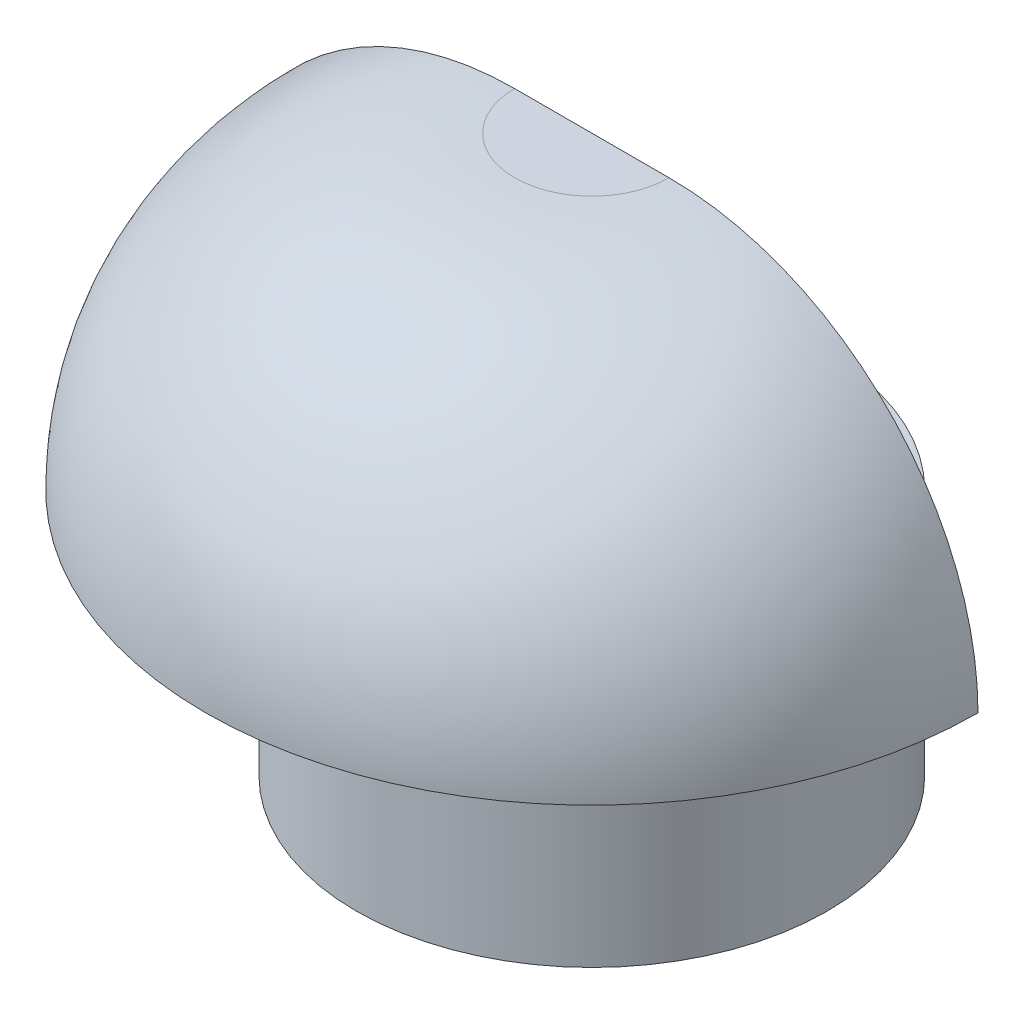
SolidWorks part; units mm, degrees
ref_plane "Front Plane" through (0, 0, 0) normal (0, 0, 1) x (1, 0, 0)
ref_plane "Top Plane" through (0, 0, 0) normal (0, 1, 0) x (1, 0, 0)
ref_plane "Right Plane" through (0, 0, 0) normal (1, 0, 0) x (0, 0, -1)
sketch "Sketch1" plane through (0, 0, 0) normal (0, 1, 0) x (1, 0, 0)
  line L0 (-12.5, 0) -> (12.5, 0)
  arc A0 (-12.5, 0) -> (12.5, 0) centre (0, 0) ccw
  dimension "D1" = 25
extrude "Boss-Extrude1" add sketch "Sketch1" along normal blind 18
fillet "Fillet1" radius 10 1 edges at (0, 18, 12.5)
sketch "Sketch2" plane through (0, 0, 0) normal (0, -1, 0) x (1, 0, 0)
  line L0 (12.5, 0) -> (-12.5, 0) construction
  line L1 (-12.5, 0) -> (-7.62, 0)
  line L2 (7.62, 0) -> (12.5, 0)
  arc A0 (-7.62, 0) -> (7.62, 0) centre (0, 0) cw
  arc A1 (-12.5, 0) -> (12.5, 0) centre (0, 0) cw
  dimension "D1" = 7.62
extrude "Cut-Extrude1" cut sketch "Sketch2" against normal blind 8
sketch "Sketch4" plane through (0, 0, 0) normal (0, -1, 0) x (1, 0, 0)
  line L0 (-7.62, 0) -> (7.62, 0)
  arc A0 (-7.62, 0) -> (7.62, 0) centre (0, 0) ccw
  dimension "D1" = 7.62
extrude "Boss-Extrude2" add sketch "Sketch4" against normal blind 8
